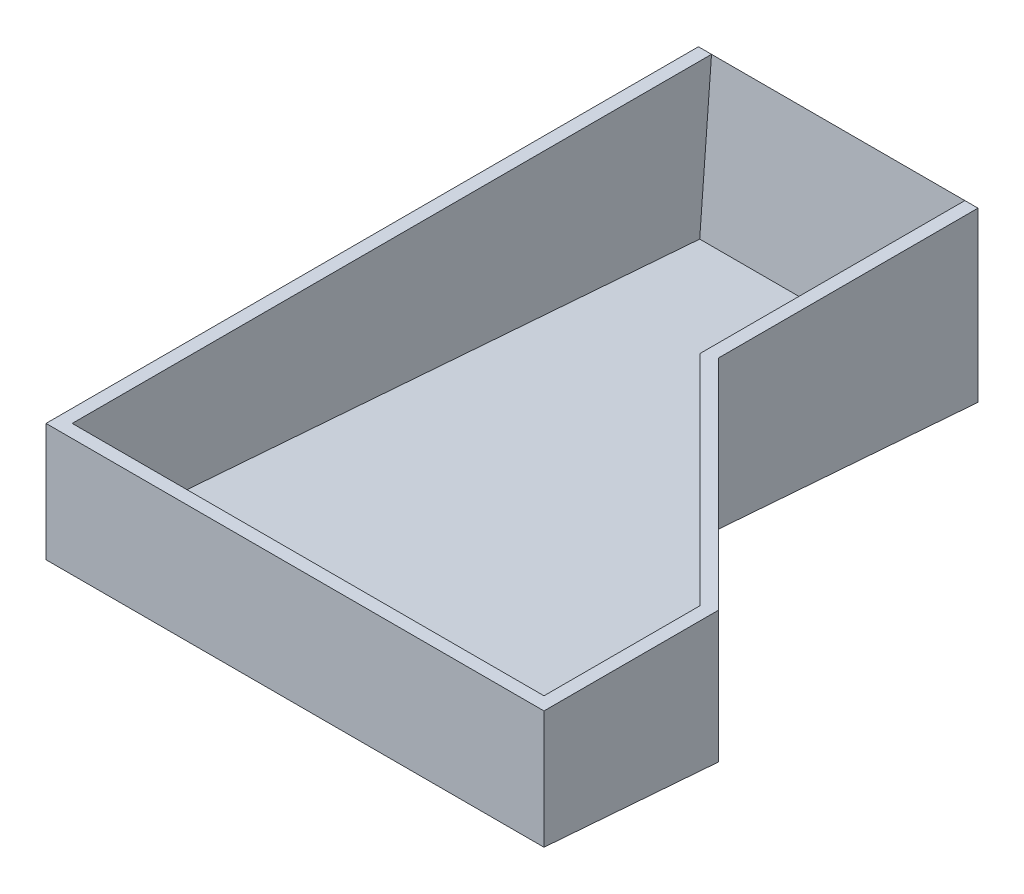
SolidWorks part; units mm, degrees
ref_plane "Front Plane" through (0, 0, 0) normal (0, 0, 1) x (1, 0, 0)
ref_plane "Top Plane" through (0, 0, 0) normal (0, 1, 0) x (1, 0, 0)
ref_plane "Right Plane" through (0, 0, 0) normal (1, 0, 0) x (0, 0, -1)
sketch "Sketch2" plane through (0, 0, 0) normal (-1, 0, 0) x (0, 0, 1)
  line L0 (0.0679, 0.5213) -> (-0.0644, 39.0211)
  line L1 (-0.0644, 39.0211) -> (149.2894, 39.5343)
  line L2 (149.2894, 39.5343) -> (149.3822, 12.5032)
  line L3 (149.3822, 12.5032) -> (0.0679, 0.5213)
  line L4 (0.0679, 0.5213) -> (0.0782, -2.4875) construction
  line L5 (100.6782, 8.5949) -> (0.0679, 0.5213) construction
  line L6 (171.0342, 10.5954) -> (171.0217, 14.2397) construction
  line L7 (-0.0644, 39.0211) -> (2.7661, 3.7475)
  line L8 (2.7661, 3.7475) -> (146.3727, 15.2714)
  line L9 (146.3727, 15.2714) -> (146.2894, 39.524)
  line L10 (2.7661, 3.7475) -> (146.2894, 39.524) construction
  line L11 (0.0679, 0.5213) -> (149.2894, 39.5343) construction
  point P3 (1.3508, 21.3843)
  dimension "D1" = 38.5
  dimension "D2" = 145
  dimension "D3" = 3
  dimension "D4" = 3
sketch "Sketch3" plane through (0, 0, 0) normal (1, 0, 0) x (0, 0, -1)
  line L8 (0, 0) -> (0, 38.5)
  line L9 (0, 38.5) -> (-149.3547, 38.5)
  line L10 (-0.0679, 0.5213) -> (0.0644, 39.0211) construction
  line L11 (0.0644, 39.0211) -> (-149.2894, 39.5343) construction
  line L12 (-149.3547, 38.5) -> (-149.3547, 11.4688)
  line L13 (0, 0) -> (-149.3547, 11.4688)
  line L14 (-149.2894, 39.5343) -> (-149.3822, 12.5032) construction
  line L15 (0, 38.5) -> (-2.7093, 3.2169)
  line L16 (-2.7093, 3.2169) -> (-146.3547, 14.2472)
  line L17 (-146.3547, 14.2472) -> (-146.3547, 38.5)
  line L18 (0.0644, 39.0211) -> (-2.7661, 3.7475) construction
  line L19 (-2.7661, 3.7475) -> (-146.3727, 15.2714) construction
  line L20 (-146.3727, 15.2714) -> (-146.2894, 39.524) construction
extrude "Boss-Extrude1" add sketch "Sketch3" along normal blind 3 contours L16 L17 L9 L12 L13 L8 L15 | L17 L16 L15 L9 region at (0, 7.2722, 74.5592) region at (0, 23.4821, 69.3415)
extrude "Boss-Extrude2" add sketch "Sketch3<3>" along normal blind 58 from surface contours L16 L17 L9 L12 L13 L8 L15 region at (0, 7.2722, 74.5592) starting at face at (3, 22.1172, 74.6773)
sketch "Sketch3<3>" plane through (0, 0, 0) normal (1, 0, 0) x (0, 0, -1) same geometry as "Sketch3"
extrude "Boss-Extrude3" add sketch "Sketch3<4>" along normal blind 3 from surface contours L17 L16 L15 L9 | L16 L17 L9 L12 L13 L8 L15 region at (0, 7.2722, 74.5592) region at (0, 23.4821, 69.3415) starting at face at (61, 20.6333, 84.8754)
sketch "Sketch3<4>" plane through (0, 0, 0) normal (1, 0, 0) x (0, 0, -1) same geometry as "Sketch3"
sketch "Sketch5" plane through (0, 38.5, 0) normal (0, 1, 0) x (1, 0, 0)
  line L0 (64, -149.3547) -> (114, -149.3547)
  line L1 (114, -149.3547) -> (114, -109.3547)
  line L2 (114, -109.3547) -> (64, -59.3547)
  line L3 (64, 0) -> (64, -149.3547) construction
  line M6 (64, -149.3547) -> (64, 0)
  dimension "D1" = 50
  dimension "D2" = 45
  dimension "D3" = 40
extrude "Boss-Extrude4" add sketch "Sketch5" against normal up to surface (27.0312 mm away) contours L1 L2 L0 M6 region at (85.7949, 38.5, 115.2521) up to face at (32, 5.7344, 74.6773)
shell "Shell1" thickness 3 removed face at (61, 23.616, 73.8547) removed face at (48.4, 38.5, 76.0128)
